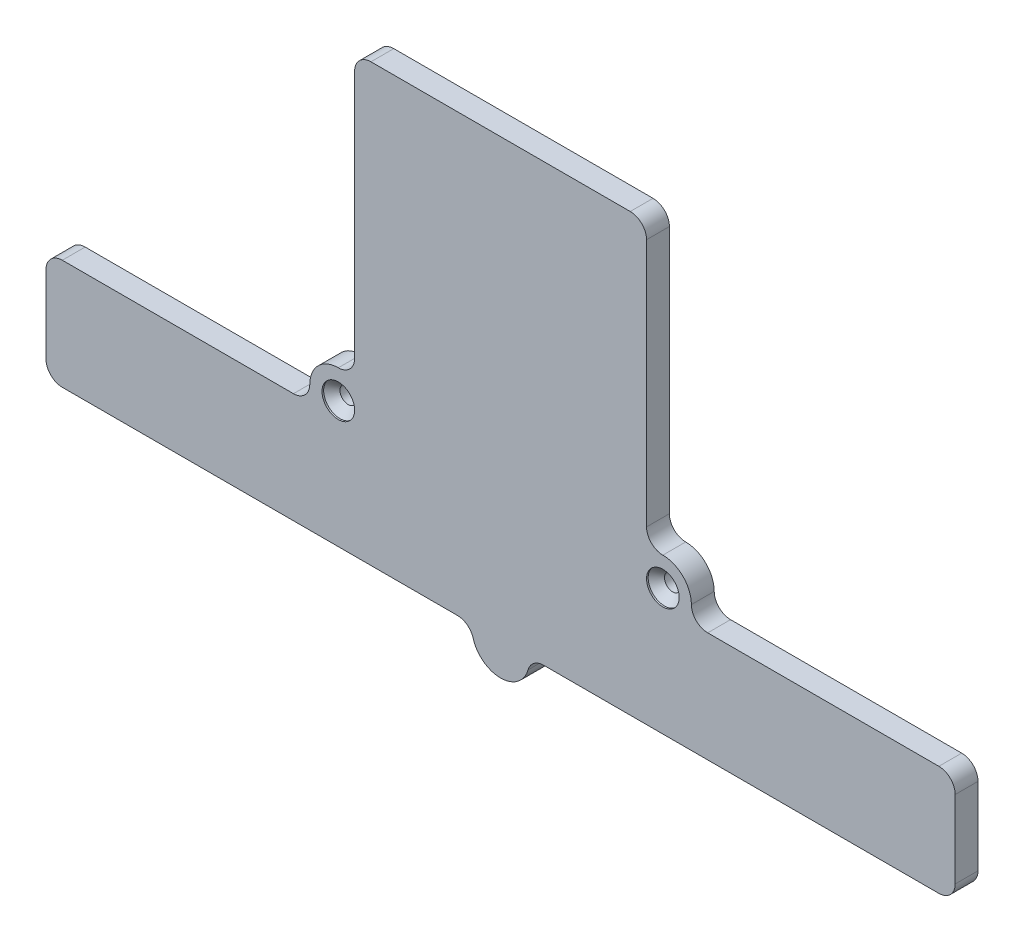
SolidWorks part; units mm, degrees
ref_plane "Front Plane" through (0, 0, 0) normal (0, 0, 1) x (1, 0, 0)
ref_plane "Top Plane" through (0, 0, 0) normal (0, 1, 0) x (1, 0, 0)
ref_plane "Right Plane" through (0, 0, 0) normal (1, 0, 0) x (0, 0, -1)
sketch "Sketch1" plane through (0, 0, 0) normal (0, 0, 1) x (1, 0, 0)
  line L8 (-53.75, -26.75) -> (-5.2915, -26.75)
  line L9 (55.75, -24.75) -> (55.75, -15.25)
  line L10 (53.75, -13.25) -> (25.4, -13.25)
  line L11 (17.9, -5.75) -> (17.9, 24.75)
  line L12 (15.9, 26.75) -> (-15.9, 26.75)
  line L13 (-17.9, 24.75) -> (-17.9, -5.75)
  line L14 (-25.4, -13.25) -> (-53.75, -13.25)
  line L15 (-55.75, -15.25) -> (-55.75, -24.75)
  line L16 (-53.75, -26.75) -> (-5.2915, -26.75)
  line L17 (55.75, -24.75) -> (55.75, -15.25)
  line L18 (53.75, -13.25) -> (25.4, -13.25)
  line L19 (17.9, -5.75) -> (17.9, 24.75)
  line L20 (15.9, 26.75) -> (-15.9, 26.75)
  line L21 (-17.9, 24.75) -> (-17.9, -5.75)
  line L22 (-25.4, -13.25) -> (-53.75, -13.25)
  line L23 (-55.75, -15.25) -> (-55.75, -24.75)
  line L66 (5.2915, -26.75) -> (53.75, -26.75)
  line L67 (5.2915, -26.75) -> (53.75, -26.75)
  arc A12 (53.75, -26.75) -> (55.75, -24.75) centre (53.75, -24.75) ccw
  arc A13 (55.75, -15.25) -> (53.75, -13.25) centre (53.75, -15.25) ccw
  arc A14 (23.4, -11.25) -> (25.4, -13.25) centre (25.4, -11.25) ccw
  arc A15 (23.4, -11.25) -> (19.9, -7.75) centre (19.9, -11.25) ccw
  arc A16 (17.9, -5.75) -> (19.9, -7.75) centre (19.9, -5.75) ccw
  arc A17 (17.9, 24.75) -> (15.9, 26.75) centre (15.9, 24.75) ccw
  arc A18 (-15.9, 26.75) -> (-17.9, 24.75) centre (-15.9, 24.75) ccw
  arc A19 (-19.9, -7.75) -> (-17.9, -5.75) centre (-19.9, -5.75) ccw
  arc A20 (-19.9, -7.75) -> (-23.4, -11.25) centre (-19.9, -11.25) ccw
  arc A21 (-25.4, -13.25) -> (-23.4, -11.25) centre (-25.4, -11.25) ccw
  arc A22 (-53.75, -13.25) -> (-55.75, -15.25) centre (-53.75, -15.25) ccw
  arc A23 (-55.75, -24.75) -> (-53.75, -26.75) centre (-53.75, -24.75) ccw
  arc A24 (53.75, -26.75) -> (55.75, -24.75) centre (53.75, -24.75) ccw
  arc A25 (55.75, -15.25) -> (53.75, -13.25) centre (53.75, -15.25) ccw
  arc A26 (23.4, -11.25) -> (25.4, -13.25) centre (25.4, -11.25) ccw
  arc A27 (23.4, -11.25) -> (19.9, -7.75) centre (19.9, -11.25) ccw
  arc A28 (17.9, -5.75) -> (19.9, -7.75) centre (19.9, -5.75) ccw
  arc A29 (17.9, 24.75) -> (15.9, 26.75) centre (15.9, 24.75) ccw
  arc A30 (-15.9, 26.75) -> (-17.9, 24.75) centre (-15.9, 24.75) ccw
  arc A31 (-19.9, -7.75) -> (-17.9, -5.75) centre (-19.9, -5.75) ccw
  arc A32 (-19.9, -7.75) -> (-23.4, -11.25) centre (-19.9, -11.25) ccw
  arc A33 (-25.4, -13.25) -> (-23.4, -11.25) centre (-25.4, -11.25) ccw
  arc A34 (-53.75, -13.25) -> (-55.75, -15.25) centre (-53.75, -15.25) ccw
  arc A35 (-55.75, -24.75) -> (-53.75, -26.75) centre (-53.75, -24.75) ccw
  arc A100 (-3.3673, -28.2045) -> (-5.2915, -26.75) centre (-5.2915, -28.75) ccw
  arc A101 (-3.3673, -28.2045) -> (-5.2915, -26.75) centre (-5.2915, -28.75) ccw
  arc A102 (-3.3673, -28.2045) -> (3.3673, -28.2045) centre (0, -27.25) ccw
  arc A103 (-3.3673, -28.2045) -> (3.3673, -28.2045) centre (0, -27.25) ccw
  arc A104 (5.2915, -26.75) -> (3.3673, -28.2045) centre (5.2915, -28.75) ccw
  arc A105 (5.2915, -26.75) -> (3.3673, -28.2045) centre (5.2915, -28.75) ccw
  dimension "D1" = 0
extrude "Boss-Extrude1" add sketch "Sketch1" along normal blind 2.8
sketch "Sketch3" plane through (0, 0, 2.8) normal (0, 0, 1) x (1, 0, 0)
  line L0 (0, 32.8811) -> (0, -41.8665) construction
  circle A0 centre (-19.9, -11.25) radius 1
  arc A1 (-19.9, -7.75) -> (-23.4, -11.25) centre (-19.9, -11.25) ccw construction
  circle A2 centre (19.9, -11.25) radius 1
  dimension "D1" = 2
extrude "Cut-Extrude1" cut sketch "Sketch3" against normal up to next
hole_wizard "CSK for M2 Flat Head Machine Screw1" positions "Sketch5" profile "Sketch4" countersink size "M2" standard "ANSI Metric" end condition through all
sketch "Sketch5" plane through (0, 0, 2.8) normal (0, 0, 1) x (1, 0, 0)
  point P0 (-19.9, -11.25)
  point P3 (19.9, -11.25)
sketch "Sketch4" plane through (-19.9, -11.25, 2.8) normal (1, 0, 0) x (0, -1, 0)
  line L0 (0, 0) -> (0, 2.8)
  line L1 (0, 2.8) -> (1, 2.8)
  line L2 (1, 2.8) -> (1, 1.2)
  line L3 (1, 1.2) -> (2, 0.2)
  line L4 (2, 0.2) -> (2, 0)
  line L6 (2, 0) -> (0, 0)
  line L7 (-1, 1.2) -> (-2, 0.2) construction
  line L11 (0, -6.35) -> (0, 107.95) construction
  dimension "Thru Hole Dia." = 2
  dimension "Thru Hole Depth" = 2.8
  dimension "C'Sink Dia." = 4
  dimension "C'Sink Angle" = 90
  dimension "Head Clearance" = 0.2
